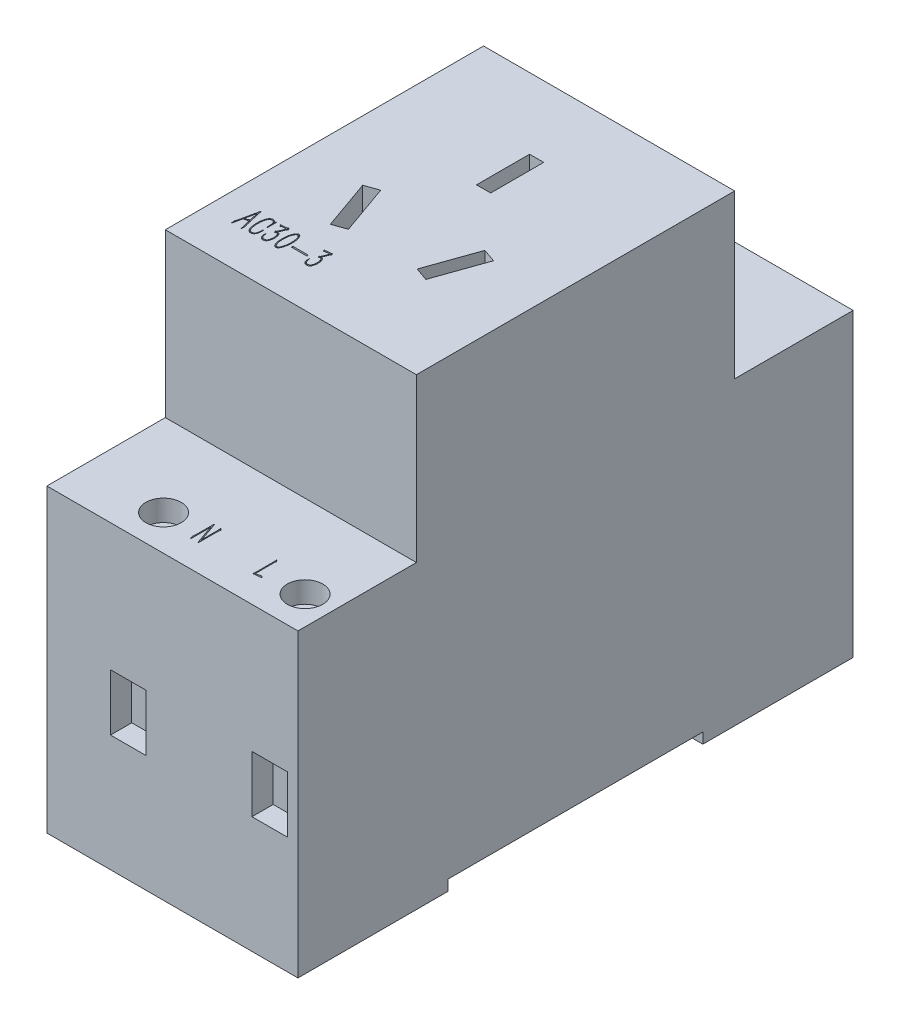
SolidWorks part; units mm, degrees
ref_plane "前视基准面" through (0, 0, 0) normal (0, 0, 1) x (1, 0, 0)
ref_plane "上视基准面" through (0, 0, 0) normal (0, 1, 0) x (1, 0, 0)
ref_plane "右视基准面" through (0, 0, 0) normal (1, 0, 0) x (0, 0, -1)
sketch "草图1" plane through (0, 0, 0) normal (1, 0, 0) x (0, 0, -1)
  line L0 (-22.5, 9.75) -> (-39.25, 9.75)
  line L1 (22.5, 32.75) -> (-22.5, 32.75)
  line L2 (22.5, 32.75) -> (22.5, 9.75)
  line L3 (22.5, -32.75) -> (18, -32.75)
  line L4 (-22.5, 32.75) -> (-22.5, 9.75)
  line L5 (22.5, 32.75) -> (-22.5, -32.75) construction
  line L6 (22.5, -32.75) -> (-22.5, 32.75) construction
  line L7 (39.25, -32.75) -> (18, -32.75)
  line L8 (39.25, -32.75) -> (39.25, 9.75)
  line L9 (39.25, 9.75) -> (22.5, 9.75)
  line L10 (-39.25, -32.75) -> (-39.25, 9.75)
  line L11 (-18, -32.75) -> (-22.5, -32.75)
  line L12 (18, -31.25) -> (-18, -31.25)
  line L13 (18, -31.25) -> (18, -32.75)
  line L14 (-18, -32.75) -> (-39.25, -32.75)
  line L15 (-18, -31.25) -> (-18, -32.75)
  line L16 (22.5, -32.75) -> (39.25, -32.75)
  line L17 (-22.5, -32.75) -> (-39.25, -32.75)
  point P0 (0, 0)
  point P10 (0, -32.75)
  dimension "D1" = 45
  dimension "D2" = 65.5
  dimension "D3" = 42.5
  dimension "D4" = 78.5
  dimension "D5" = 16.75
  dimension "D6" = 36
extrude "凸台-拉伸1" add sketch "草图1" along normal mid plane 35.5 contours L15 L12 L13 L3 L7 L8 L9 L2 L1 L4 L0 L10 L14 L11 region at (0, -3.3922, 0)
sketch "草图2" plane through (0, 9.75, 0) normal (0, 1, 0) x (1, 0, 0)
  line L0 (17.75, -39.25) -> (-17.75, -39.25) construction
  line L1 (-17.75, -22.5) -> (-17.75, -39.25) construction
  circle A0 centre (-6.25, -34.25) radius 2.5
  dimension "D1" = 5
  dimension "D3" = 11.5
  dimension "D2" = 5
extrude "切除-拉伸1" cut sketch "草图2" against normal blind 3
sketch "草图3" plane through (0, 0, 39.25) normal (0, 0, 1) x (1, 0, 0)
  line L0 (-17.75, -32.75) -> (-17.75, 9.75) construction
  line L1 (-8.75, -8.25) -> (-3.75, -8.25)
  line L2 (-8.75, -8.25) -> (-8.75, -16.25)
  line L3 (-8.75, -16.25) -> (-3.75, -16.25)
  line L4 (-3.75, -8.25) -> (-3.75, -16.25)
  line L5 (17.75, 9.75) -> (-17.75, 9.75) construction
  dimension "D1" = 5
  dimension "D2" = 8
  dimension "D3" = 9
  dimension "D4" = 18
extrude "切除-拉伸2" cut sketch "草图3" against normal blind 3
pattern_linear "阵列(线性)1" count 3 spacing 20 along (1, 0, 0) of "切除-拉伸2", "切除-拉伸1"
sketch "草图5" plane through (0, 9.75, 0) normal (0, 1, 0) x (1, 0, 0)
  circle A0 centre (0, 30.875) radius 3
  dimension "D1" = 6
extrude "切除-拉伸3" cut sketch "草图5" against normal blind 3
sketch "草图6" plane through (0, 0, -39.25) normal (0, 0, -1) x (-1, 0, 0)
  line L1 (-2.4489, -8.4358) -> (2.5511, -8.4358)
  line L2 (-2.4489, -8.4358) -> (-2.4489, -16.4358)
  line L3 (-2.4489, -16.4358) -> (2.5511, -16.4358)
  line L4 (2.5511, -8.4358) -> (2.5511, -16.4358)
  line L5 (-2.4489, -8.4358) -> (2.5511, -16.4358) construction
  line L6 (-2.4489, -16.4358) -> (2.5511, -8.4358) construction
  point P0 (0.0511, -12.4358)
  dimension "D1" = 5
  dimension "D2" = 8
extrude "切除-拉伸4" cut sketch "草图6" against normal blind 3
sketch "草图9" plane through (0, 32.75, 0) normal (0, 1, 0) x (1, 0, 0)
  text T0 "\r\n            \r\n\r\n\r\n\r\n\r\n  AC30-3"
extrude "切除-拉伸6" cut sketch "草图9" against normal blind 0.3
sketch "草图11" plane through (0, 0, 36.25) normal (0, 0, 1) x (1, 0, 0)
  point P0 (-6.25, -12.25)
  point P1 (13.75, -12.25)
sketch "1_0_Point" plane through (0, 0, -36.25) normal (0, 0, -1) x (-1, 0, 0)
  point P0 (0, -12.4358)
sketch "草图13" plane through (0, 9.75, 0) normal (0, 1, 0) x (1, 0, 0)
  text T0 "\r\n\r\n         N    L "
  text T1 "\r\n   PE"
extrude "切除-拉伸7" cut sketch "草图13" against normal blind 0.3
sketch "草图14" plane through (0, 32.75, 0) normal (0, 1, 0) x (1, 0, 0)
  line L0 (0, 0) -> (0, -9.5)
  line L1 (-1.25, 12.5) -> (0.75, 12.5)
  line L2 (-1.25, 12.5) -> (-1.25, 5)
  line L3 (-1.25, 5) -> (0.75, 5)
  line L4 (0.75, 12.5) -> (0.75, 5)
  line L5 (-7.3644, -2.4289) -> (-9.25, -3.0956)
  line L6 (-6.75, -10.1667) -> (-9.25, -3.0956)
  line L7 (-4.8644, -9.5) -> (-7.3644, -2.4289)
  line L8 (4.8644, -9.5) -> (6.75, -10.1667)
  line L9 (4.8644, -9.5) -> (7.3644, -2.4289)
  line L10 (6.75, -10.1667) -> (9.25, -3.0956)
  line L11 (7.3644, -2.4289) -> (9.25, -3.0956)
  line L12 (17.75, 22.5) -> (-17.75, 22.5) construction
  line L13 (17.75, 22.5) -> (17.75, -22.5) construction
  line L14 (17.75, -22.5) -> (-17.75, -22.5) construction
  line L16 (-4.8644, -9.5) -> (-6.75, -10.1667)
  dimension "D1" = 10
  dimension "D2" = 7.5
  dimension "D3" = 17
  dimension "D4" = 2
  dimension "D5" = 8.5
  dimension "D6" = 11
  dimension "D7" = 2
  dimension "D8" = 7.5
  dimension "D9" = 13
extrude "切除-拉伸8" cut sketch "草图14" against normal blind 5 contours L4 L1 L2 L3 | L11 L9 L8 L10 | L16 L7 L5 L6 region at (-0.25, 32.75, -8.75) region at (-7.0572, 32.75, 6.2978) region at (7.0572, 32.75, 6.2978)
sketch "草图15" plane through (0, 27.75, 0) normal (0, 1, 0) x (1, 0, 0)
  point P0 (-0.25, 8.75)
  point P1 (-7.2691, -6.6311)
  point P2 (6.9385, -6.6311)
sketch "0_0_Point" plane through (0, 0, 36.25) normal (0, 0, 1) x (1, 0, 0)
  point P0 (13.75, -12.25)
other "0_0" parameters "直径"=2, "端头长度"=2
ref_axis "基准轴1" through (13.75, -12.25, 46.25) along (0, 0, -1)
sketch "0_1_Point" plane through (0, 0, 36.25) normal (0, 0, 1) x (1, 0, 0)
  point P0 (-6.25, -12.25)
other "0_1" parameters "直径"=2, "端头长度"=2
ref_axis "基准轴2" through (-6.25, -12.25, 46.25) along (0, 0, -1)
other "1_0" parameters "直径"=2, "端头长度"=2
ref_axis "基准轴3" through (0, -12.4358, -46.25) along (0, 0, 1)
